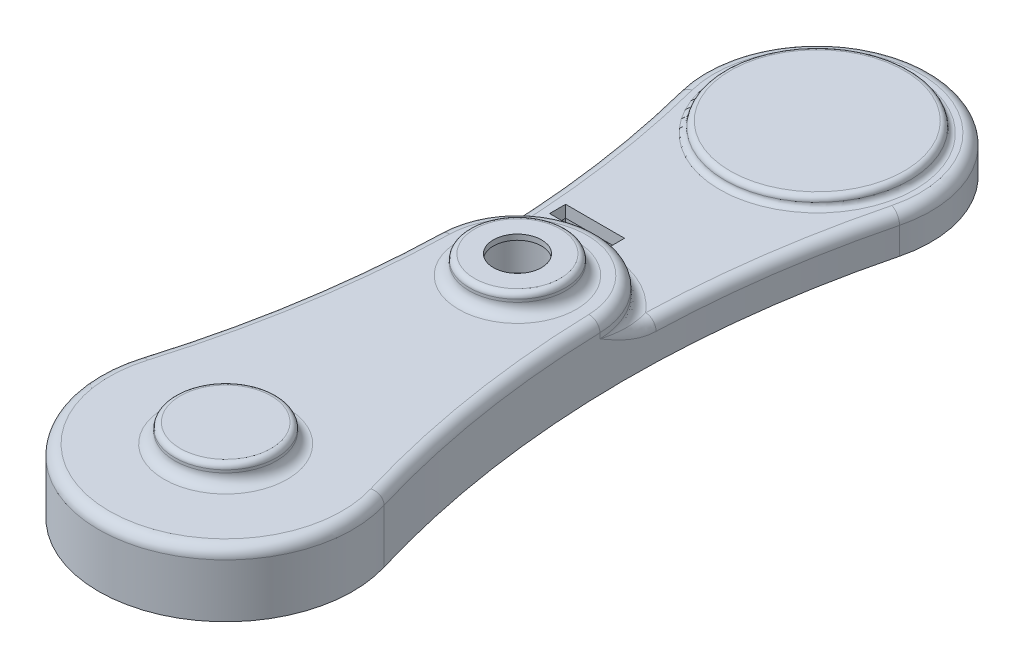
SolidWorks part; units mm, degrees
ref_plane "Front" through (0, 0, 0) normal (0, 0, 1) x (1, 0, 0)
ref_plane "Top" through (0, 0, 0) normal (0, 1, 0) x (1, 0, 0)
ref_plane "Right" through (0, 0, 0) normal (1, 0, 0) x (0, 0, -1)
sketch "Эскиз1" plane through (0, 0, 0) normal (0, 1, 0) x (1, 0, 0)
  line L0 (0, 0) -> (0, 112) construction
  line L3 (0, 0) -> (0, -109) construction
  arc A0 (-29.5542, 81.4582) -> (29.5542, 81.4582) centre (0, 112) ccw
  circle A1 centre (0, 0) radius 30
  arc A2 (-45.4839, -95.3082) -> (45.4839, -95.3082) centre (0, -109) ccw
  arc A3 (-45.4839, -95.3082) -> (-41.1915, 101.5351) centre (-398.1421, 10.8505) ccw
  arc A4 (41.1915, 101.5351) -> (45.4839, -95.3082) centre (398.1421, 10.8505) ccw
  arc A5 (-38.781, -97.326) -> (-34.407, 103.2588) centre (-398.1421, 10.8505) ccw
  arc A6 (34.407, 103.2588) -> (38.781, -97.326) centre (398.1421, 10.8505) ccw
  circle A7 centre (0, 112) radius 35.5
  circle A8 centre (0, -109) radius 40.5
  arc A9 (41.1915, 101.5351) -> (-41.1915, 101.5351) centre (0, 112) ccw
  circle A10 centre (0, 112) radius 42.5 construction
  arc A11 (32.6969, -74.5448) -> (-32.6969, -74.5448) centre (0, -109) ccw
  circle A12 centre (0, -109) radius 47.5 construction
  circle A13 centre (0, 0) radius 23
  point P23 (43.0337, 125.1567)
  point P26 (43.0337, -95.8433)
  dimension "D2" = 85
  dimension "D3" = 60
  dimension "D5" = 95
  dimension "D1" = 112
  dimension "D4" = 109
  dimension "D6" = 7
  dimension "D7" = 7
  dimension "D8" = 7
extrude "Бобышка-Вытянуть1" add sketch "Эскиз1" along normal blind 31 contours A7 | A4 A9 A3 A1 A5 A7 A6 | A6 A1 A5 | A6 A0 A5 A1 | A7 A5 A0 A6 | A1 A5 | A1 A6 | A8 A5 A1 A3 A2 A4 A6 | A11 A6 A1 A5 | A6 A11 A5 A8 | A8 | A13 | A13 A6 A1 A5 region at (-31.0702, 0, -92.5611) region at (-26.702, 0, -50.3429) region at (0, 0, -50.6445) region at (0, 0, -112) region at (-25.9119, 0, -0.7062) region at (0, 0, -29.4544) region at (25.9119, 0, -0.7062) region at (-30.3292, 0, 9.684) region at (-0.3211, 0, 23.5666) region at (0, 0, 0) region at (0, 0, 46.5445) region at (0, 0, 62.3544) region at (0, 0, 109)
extrude "Вырез-Вытянуть1" cut sketch "Эскиз1<3>" along normal blind 17 contours A8 | A6 A11 A5 A8 | A11 A6 A1 A5 | A13 A5 A1 A6 | A13 region at (-0.3211, 0, 23.5666) region at (0, 0, 0) region at (0, 0, 46.5445) region at (0, 0, 62.3544) region at (0, 0, 109)
sketch "Эскиз1<3>" plane through (0, 0, 0) normal (0, 1, 0) x (1, 0, 0) same geometry as "Эскиз1"
sketch "Эскиз3" plane through (0, 0, 0) normal (0, 1, 0) x (1, 0, 0)
  circle A0 centre (0, 0) radius 9
  circle A1 centre (0, 0) radius 11
  dimension "D1" = 22
  dimension "D2" = 22
  dimension "D3" = 18
extrude "Вырез-Вытянуть2" cut sketch "Эскиз3" along normal through all contours A0
extrude "Вырез-Вытянуть3" cut sketch "Эскиз3<6>" along normal blind 29 contours A1
sketch "Эскиз3<6>" plane through (0, 0, 0) normal (0, 1, 0) x (1, 0, 0) same geometry as "Эскиз3"
sketch "Эскиз4" plane through (0, 0, 0) normal (0, 1, 0) x (1, 0, 0)
  circle A2 centre (0, 0) radius 30
  circle A4 centre (0, 112) radius 115.1561
  dimension "D1" = 60
extrude "Вырез-Вытянуть4" cut sketch "Эскиз4" along normal through all from offset 18 contours A2 region at (0, 0, -115.8081)
sketch "Эскиз5" plane through (0, 0, 0) normal (0, -1, 0) x (1, 0, 0)
  circle A0 centre (0, -112) radius 25
  circle A1 centre (0, -112) radius 27.5
  circle A2 centre (0, -112) radius 35.5
  dimension "D1" = 55
  dimension "D2" = 50
  dimension "D3" = 71
extrude "Вырез-Вытянуть5" cut sketch "Эскиз5" against normal blind 12 contours A1
extrude "Вырез-Вытянуть6" cut sketch "Эскиз5<3>" against normal blind 15 contours A0
sketch "Эскиз5<3>" plane through (0, 0, 0) normal (0, -1, 0) x (1, 0, 0) same geometry as "Эскиз5"
extrude "Cut-Extrude2" cut sketch "Эскиз5<4>" against normal blind 1.5 contours A2
sketch "Эскиз5<4>" plane through (0, 0, 0) normal (0, -1, 0) x (1, 0, 0) same geometry as "Эскиз5"
sketch "Эскиз6" plane through (0, 0, 0) normal (0, 1, 0) x (1, 0, 0)
  line L0 (0, 34) -> (0, 39)
  line L1 (0, 39) -> (-26, 39)
  line L2 (-26, 39) -> (-26, 44)
  line L3 (-26, 44) -> (0, 44)
  line L4 (0, -50) -> (0, 50) construction
  line L5 (0, 44) -> (0, 39)
  line L6 (-26, 39) -> (-26, 34)
  line L7 (-26, 34) -> (0, 34)
  line L8 (-24, 39) -> (-24, 42)
  line L9 (-24, 42) -> (-2, 42)
  line L10 (-2, 42) -> (-2, 39)
  line L11 (-24, 39) -> (-24, 36)
  line L12 (-24, 36) -> (-2, 36)
  line L13 (-2, 36) -> (-2, 39)
  dimension "D1" = 26
  dimension "D2" = 39
  dimension "D3" = 2
  dimension "D4" = 2
extrude "Вырез-Вытянуть7" cut sketch "Эскиз6" along normal through all contours L10 L9 L8 L1 | L12 L13 L1 L11 region at (-13, 0, -37.5) region at (-13, 0, -40.5)
extrude "Вырез-Вытянуть8" cut sketch "Эскиз6<3>" along normal blind 9.5 contours L9 L10 L1 L5 L3 L2 L8 | L13 L12 L11 L1 L6 L7 L0 region at (-13, 0, -35.4687) region at (-13, 0, -42.5312)
sketch "Эскиз6<3>" plane through (0, 0, 0) normal (0, 1, 0) x (1, 0, 0) same geometry as "Эскиз6"
extrude "Вырез-Вытянуть9" cut sketch "Эскиз6<4>" along normal through all from offset 14.5 contours L9 L10 L1 L5 L3 L2 L8 | L13 L12 L11 L1 L6 L7 L0 region at (-13, 0, -35.4687) region at (-13, 0, -42.5312)
sketch "Эскиз6<4>" plane through (0, 0, 0) normal (0, 1, 0) x (1, 0, 0) same geometry as "Эскиз6"
sketch "Sketch1" plane through (0, 0, 0) normal (0, 1, 0) x (1, 0, 0)
  line L0 (0, 0) -> (0, 48)
  line L1 (0, 48) -> (-95.7336, 48)
  line L2 (0, 48) -> (4, 48)
  line L3 (4, 48) -> (4, 29.7321)
  circle A1 centre (0, 112) radius 34.5
  circle A6 centre (0, 0) radius 30
  circle A7 centre (0, 112) radius 115.1561
  dimension "D1" = 60
  dimension "D2" = 69
extrude "Cut-Extrude1" cut sketch "Sketch1" along normal through all from offset 14 contours A1 | L1 A7 A6 L0 | A6 L3 L2 L0 region at (-44.3031, 0, -31.4577) region at (2.0049, 0, -38.9553) region at (-47.8668, 0, -51.2291)
sketch "Эскиз7" plane through (0, 0, 0) normal (1, 0, 0) x (0, 0, -1)
  line L0 (0, 0) -> (0, 5)
  line L1 (0, 5) -> (39, 5)
  line L3 (42.2909, 5) -> (40.6454, 7.85)
  line L4 (40.6454, 7.85) -> (37.3546, 7.85)
  line L5 (37.3546, 7.85) -> (35.7091, 5)
  line L6 (35.7091, 5) -> (37.3546, 2.15)
  line L7 (37.3546, 2.15) -> (40.6454, 2.15)
  line L8 (40.6454, 2.15) -> (42.2909, 5)
  circle A0 centre (39, 5) radius 1.5
  circle A1 centre (39, 5) radius 3.25
  circle A2 centre (39, 5) radius 2.85 construction
  dimension "D3" = 5.7
  dimension "D4" = 6.5
  dimension "D5" = 3
  dimension "D1" = 39
  dimension "D2" = 5
extrude "Вырез-Вытянуть10" cut sketch "Эскиз7" against normal through all contours A0
extrude "Вырез-Вытянуть11" cut sketch "Эскиз7<3>" along normal blind 10 from offset 28 contours L5 L6 L7 L8 L3 L4 offset against normal yes
sketch "Эскиз7<3>" plane through (0, 0, 0) normal (1, 0, 0) x (0, 0, -1) same geometry as "Эскиз7"
extrude "Вырез-Вытянуть12" cut sketch "Эскиз7<4>" against normal through all from offset 30.5 contours A1 offset against normal yes
sketch "Эскиз7<4>" plane through (0, 0, 0) normal (1, 0, 0) x (0, 0, -1) same geometry as "Эскиз7"
sketch "Sketch2" plane through (0, 0, 0) normal (0, 1, 0) x (1, 0, 0)
  circle A0 centre (0, 0) radius 18
  circle A1 centre (0, 0) radius 187.5906
  circle A2 centre (0, -109) radius 19
  circle A3 centre (0, -109) radius 12
  dimension "D1" = 36
  dimension "D2" = 38
  dimension "D3" = 24
extrude "Cut-Extrude3" cut sketch "Sketch2" along normal through all from offset 24 contours A1 A2 A0 region at (-182.2848, 0, 0)
extrude "Cut-Extrude4" cut sketch "Sketch2<3>" along normal blind 24 contours A3 region at (0, 0, 109)
sketch "Sketch2<3>" plane through (0, 0, 0) normal (0, 1, 0) x (1, 0, 0) same geometry as "Sketch2"
fillet "Fillet12" radius 4 3 edges at (0, 24, 128) (0, 24, 18) (0, 14, -30)
fillet "Fillet13" radius 2 4 edges at (0, 14, -77.5) (0, 18, -77.5) (0, 31, 128) (0, 31, 18)
fillet "Fillet14" radius 4 9 edges at (0, 24, 156.5) (34.5457, 24, 47.7598) (0, 24, -30) (-29.8571, 15.1726, -8.9532) (29.8571, 15.1726, -8.9532) (33.0397, 14, -59.2002) (0, 14, -154.5) (-34.5457, 24, 47.7598) (-33.0397, 14, -59.2002)
